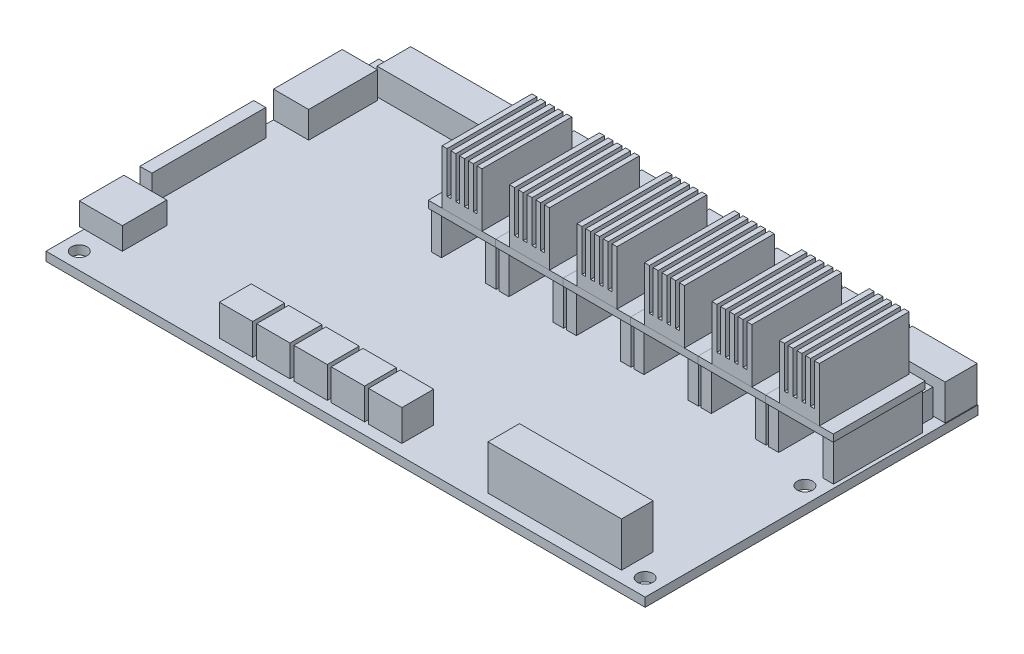
SolidWorks part; units mm, degrees
ref_plane "Front Plane" through (0, 0, 0) normal (0, 0, 1) x (1, 0, 0)
ref_plane "Top Plane" through (0, 0, 0) normal (0, 1, 0) x (1, 0, 0)
ref_plane "Right Plane" through (0, 0, 0) normal (1, 0, 0) x (0, 0, -1)
sketch "Sketch1" plane through (0, 0, 0) normal (0, 1, 0) x (1, 0, 0)
  line L0 (79.3265, 56.5678) -> (214.3208, 56.5586) construction
  line L1 (73.414, 57.737) -> (208.414, 57.6311) construction
  line L2 (79.3208, 56.5586) -> (214.3208, 56.5586)
  line L3 (79.3208, 56.5586) -> (79.3208, 131.5586)
  line L4 (79.3208, 131.5586) -> (214.3208, 131.5586)
  line L5 (214.3208, 56.5586) -> (214.3208, 131.5586)
  line L6 (20.34, 42.1896) -> (155.34, 42.1896) construction
  line L7 (79.3124, 56.5845) -> (214.3124, 56.5845) construction
  circle A0 centre (83.0708, 127.8086) radius 1.75
  circle A1 centre (83.0708, 60.3086) radius 1.75
  circle A2 centre (210.5708, 60.3086) radius 1.75
  circle A3 centre (210.5708, 96.3086) radius 1.75
  dimension "D4" = 3.75
  dimension "D11" = 3.5
  dimension "D1" = 135
  dimension "D2" = 75
  dimension "D3" = 135
  dimension "D5" = 3.75
  dimension "D6" = 3.75
  dimension "D7" = 36
  dimension "D8" = 3.75
  dimension "D9" = 135
  dimension "D10" = 135
sketch "Sketch2" plane through (0, 0, 0) normal (0, 1, 0) x (1, 0, 0)
  line L1 (122.8895, 119.905) -> (125.1527, 119.905)
  line L2 (122.8895, 119.905) -> (122.8895, 99.8243)
  line L3 (122.8895, 99.8243) -> (125.1527, 99.8243)
  line L4 (125.1527, 119.905) -> (125.1527, 99.8243)
  line L5 (135.1124, 119.905) -> (137.4989, 119.905)
  line L6 (135.1124, 119.905) -> (135.1124, 99.8243)
  line L7 (135.1124, 99.8243) -> (137.4989, 99.8243)
  line L8 (137.4989, 119.905) -> (137.4989, 99.8243)
extrude "Boss-Extrude1" add sketch "Sketch2" along normal blind 8.5
sketch "Sketch4" plane through (0, 8.5, 0) normal (0, 1, 0) x (1, 0, 0)
  line L1 (122.5341, 120.184) -> (137.7931, 120.184)
  line L2 (122.5341, 120.184) -> (122.5341, 99.4755)
  line L3 (122.5341, 99.4755) -> (137.7931, 99.4755)
  line L4 (137.7931, 120.184) -> (137.7931, 99.4755)
extrude "Boss-Extrude4" add sketch "Sketch4" along normal blind 1.6 separate body
sketch "Sketch6" plane through (0, 0, -99.4755) normal (0, 0, 1) x (1, 0, 0)
  line L0 (122.5341, 10.1) -> (137.7931, 10.1) construction
  line L1 (125.6473, 10.1) -> (134.6473, 10.1)
  line L2 (125.6473, 10.1) -> (125.6473, 22.2803)
  line L3 (125.6473, 22.2803) -> (126.7689, 22.2803)
  line L4 (134.6473, 10.1) -> (134.6473, 22.2803)
  line L5 (126.7689, 22.2803) -> (126.7689, 12.9302)
  line L6 (126.7689, 12.9302) -> (127.6168, 12.9302)
  line L7 (127.6168, 12.9302) -> (127.6168, 22.2803)
  line L8 (133.5256, 22.2803) -> (133.5256, 12.9302)
  line L9 (133.5256, 12.9302) -> (132.6777, 12.9302)
  line L10 (132.6777, 12.9302) -> (132.6777, 22.2803)
  line L11 (131.556, 22.2803) -> (131.556, 12.9302)
  line L12 (131.556, 12.9302) -> (130.7081, 12.9302)
  line L13 (130.7081, 12.9302) -> (130.7081, 22.2803)
  line L14 (128.7385, 22.2803) -> (128.7385, 12.9302)
  line L15 (128.7385, 12.9302) -> (129.5864, 12.9302)
  line L16 (129.5864, 12.9302) -> (129.5864, 22.2803)
  line L17 (127.6168, 22.2803) -> (128.7385, 22.2803)
  line L18 (129.5864, 22.2803) -> (130.7081, 22.2803)
  line L19 (131.556, 22.2803) -> (132.6777, 22.2803)
  line L20 (133.5256, 22.2803) -> (134.6473, 22.2803)
  dimension "D1" = 9
  dimension "D2" = 12.1803
extrude "Boss-Extrude5" add sketch "Sketch6" against normal blind 20.25 separate body
pattern_linear "LPattern1" count 6 spacing 15.2 along (1, 0, 0) of "Boss-Extrude4", "Boss-Extrude5", "Boss-Extrude1"
sketch "Sketch7" plane through (0, 0, 0) normal (0, 1, 0) x (1, 0, 0)
  line L1 (78.2741, 75.1639) -> (87.935, 75.1639)
  line L2 (78.2741, 75.1639) -> (78.2741, 65.1301)
  line L3 (78.2741, 65.1301) -> (87.935, 65.1301)
  line L4 (87.935, 75.1639) -> (87.935, 65.1301)
extrude "Boss-Extrude6" add sketch "Sketch7" along normal blind 5 separate body
sketch "Sketch8" plane through (0, 0, 0) normal (0, 1, 0) x (1, 0, 0)
  line L1 (115.8103, 66.3127) -> (123.3281, 66.3127)
  line L2 (115.8103, 66.3127) -> (115.8103, 59.1305)
  line L3 (115.8103, 59.1305) -> (123.3281, 59.1305)
  line L4 (123.3281, 66.3127) -> (123.3281, 59.1305)
extrude "Boss-Extrude7" add sketch "Sketch8" along normal blind 7 separate body
pattern_linear "LPattern2" count 5 spacing 8.4 along (1, 0, 0) of "Boss-Extrude7"
sketch "Sketch9" plane through (0, 0, 0) normal (0, 1, 0) x (1, 0, 0)
  line L1 (176.3086, 66.2535) -> (206.4123, 66.2535)
  line L2 (176.3086, 66.2535) -> (176.3086, 59.1496)
  line L3 (176.3086, 59.1496) -> (206.4123, 59.1496)
  line L4 (206.4123, 66.2535) -> (206.4123, 59.1496)
extrude "Boss-Extrude8" add sketch "Sketch9" along normal blind 10 separate body
sketch "Sketch10" plane through (0, 0, 0) normal (0, 1, 0) x (1, 0, 0)
  line L0 (79.3208, 56.5586) -> (79.3208, 131.5586) construction
  line L1 (79.3208, 103.3733) -> (82.0279, 103.3733)
  line L2 (79.3208, 103.3733) -> (79.3208, 77.7093)
  line L3 (79.3208, 77.7093) -> (82.0279, 77.7093)
  line L4 (82.0279, 103.3733) -> (82.0279, 77.7093)
  line L5 (79.3208, 131.5586) -> (214.3208, 131.5586) construction
  line L6 (79.3208, 123.2933) -> (87.2565, 123.2933)
  line L7 (79.3208, 123.2933) -> (79.3208, 107.8093)
  line L8 (79.3208, 107.8093) -> (87.2565, 107.8093)
  line L9 (87.2565, 123.2933) -> (87.2565, 107.8093)
  line L10 (86.4891, 131.5586) -> (123.145, 131.5586)
  line L11 (86.4891, 131.5586) -> (86.4891, 123.9704)
  line L12 (86.4891, 123.9704) -> (123.145, 123.9704)
  line L13 (123.145, 131.5586) -> (123.145, 123.9704)
  line L15 (125.5674, 123.9704) -> (135.636, 123.9704)
  line L16 (125.5674, 123.9704) -> (125.5674, 121.2727)
  line L17 (125.5674, 121.2727) -> (135.636, 121.2727)
  line L18 (135.636, 123.9704) -> (135.636, 121.2727)
  line L19 (140.6702, 123.9704) -> (150.8731, 123.9704)
  line L20 (140.6702, 123.9704) -> (140.6702, 121.2727)
  line L21 (140.6702, 121.2727) -> (150.8731, 121.2727)
  line L22 (150.8731, 123.9704) -> (150.8731, 121.2727)
  line L23 (156.1087, 123.9704) -> (166.3786, 123.9704)
  line L24 (156.1087, 123.9704) -> (156.1087, 121.2727)
  line L25 (156.1087, 121.2727) -> (166.3786, 121.2727)
  line L26 (166.3786, 123.9704) -> (166.3786, 121.2727)
  line L27 (171.0102, 123.9704) -> (181.2801, 123.9704)
  line L28 (171.0102, 123.9704) -> (171.0102, 121.2727)
  line L29 (171.0102, 121.2727) -> (181.2801, 121.2727)
  line L30 (181.2801, 123.9704) -> (181.2801, 121.2727)
  line L31 (186.5158, 123.9704) -> (196.6514, 123.9704)
  line L32 (186.5158, 123.9704) -> (186.5158, 121.2727)
  line L33 (186.5158, 121.2727) -> (196.6514, 121.2727)
  line L34 (196.6514, 123.9704) -> (196.6514, 121.2727)
  line L35 (201.4844, 123.956) -> (211.7543, 123.956)
  line L36 (201.4844, 123.956) -> (201.4844, 121.2727)
  line L37 (201.4844, 121.2727) -> (211.7543, 121.2727)
  line L38 (211.7543, 123.956) -> (211.7543, 121.2727)
extrude "Boss-Extrude9" add sketch "Sketch10" along normal blind 6 separate body
sketch "Sketch11" plane through (0, 0, 0) normal (0, 1, 0) x (1, 0, 0)
  line L0 (79.3208, 131.5586) -> (214.3208, 131.5586) construction
  line L1 (123.2878, 131.5586) -> (137.9001, 131.5586)
  line L2 (123.2878, 131.5586) -> (123.2878, 124.3317)
  line L3 (123.2878, 124.3317) -> (137.9001, 124.3317)
  line L4 (137.9001, 131.5586) -> (137.9001, 124.3317)
extrude "Boss-Extrude10" add sketch "Sketch11" along normal blind 8 separate body
pattern_linear "LPattern3" count 6 spacing 15.25 along (1, 0, 0) of "Boss-Extrude10"
sketch "Sketch12" plane through (0, 0, 0) normal (0, 1, 0) x (1, 0, 0)
  line L1 (79.3208, 131.5586) -> (214.3208, 131.5586)
  line L2 (79.3208, 131.5586) -> (79.3208, 56.5586)
  line L3 (79.3208, 56.5586) -> (214.3208, 56.5586)
  line L4 (214.3208, 131.5586) -> (214.3208, 56.5586)
  circle A0 centre (83.0708, 127.8086) radius 1.75
  circle A1 centre (83.0708, 60.3086) radius 1.75
  circle A2 centre (210.5708, 60.3086) radius 1.75
  circle A3 centre (210.5708, 96.3086) radius 1.75
extrude "Boss-Extrude12" add sketch "Sketch12" against normal blind 2 separate body
